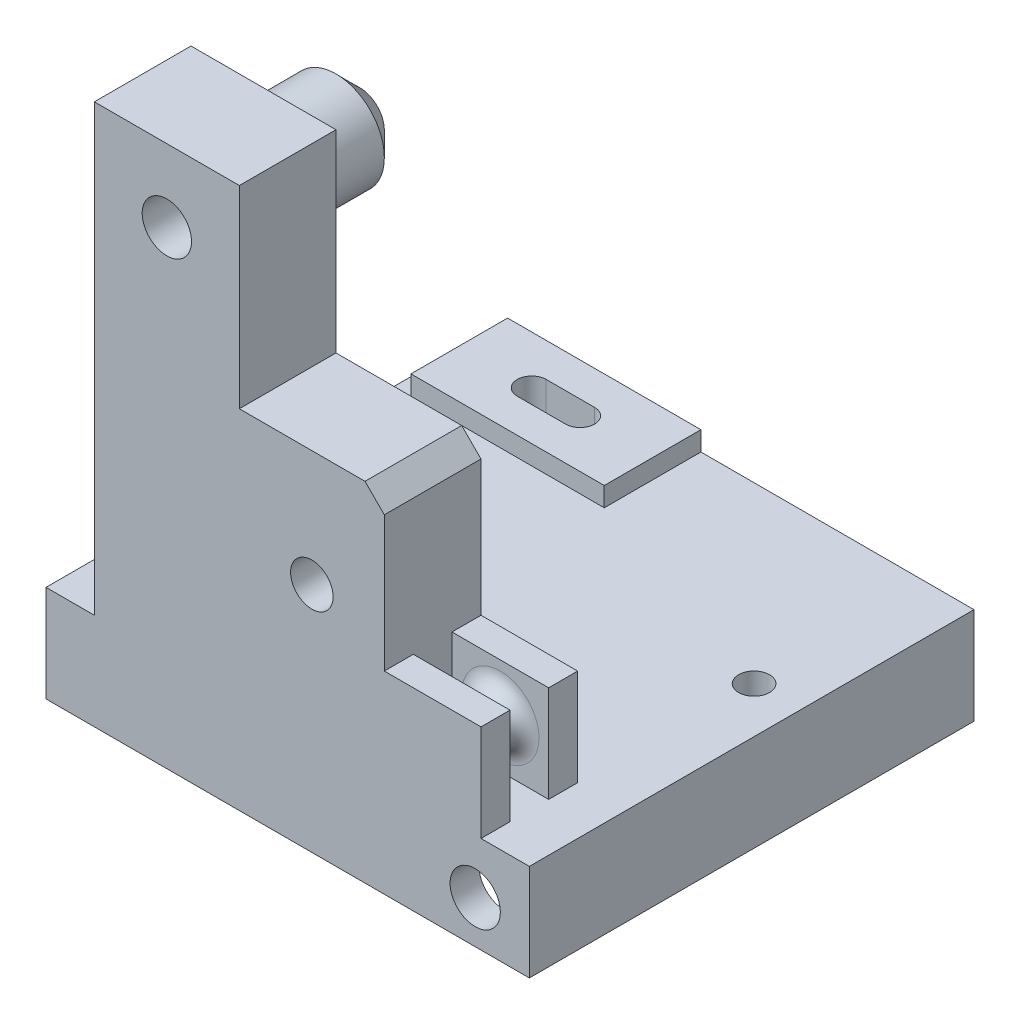
SolidWorks part; units mm, degrees
ref_plane "Front Plane" through (0, 0, 0) normal (0, 0, 1) x (1, 0, 0)
ref_plane "Top Plane" through (0, 0, 0) normal (0, 1, 0) x (1, 0, 0)
ref_plane "Right Plane" through (0, 0, 0) normal (1, 0, 0) x (0, 0, -1)
sketch "Sketch1" plane through (0, 0, 0) normal (0, 0, 1) x (1, 0, 0)
  line L0 (-15, 0) -> (-15, 46)
  line L1 (-15, 46) -> (0, 46)
  line L2 (0, 46) -> (0, 26)
  line L5 (0, 26) -> (15, 26)
  line L6 (15, 26) -> (15, 0)
  line L12 (-15, 0) -> (15, 0)
  circle A0 centre (-7.5, 38.5) radius 2.55
  circle A1 centre (7.5, 14) radius 2.2
  point P8 (0, 0)
  point P12 (-7.5, 46)
  point P16 (7.5, 26)
  dimension "D7" = 5.1
  dimension "D9" = 4.4
  dimension "D1" = 46
  dimension "D2" = 15
  dimension "D3" = 30
  dimension "D6" = 20
  dimension "D8" = 7.5
  dimension "D10" = 12
extrude "Boss-Extrude1" add sketch "Sketch1" along normal blind 6 and the other way blind 4
sketch "Sketch2" plane through (15, 0, 0) normal (1, 0, 0) x (0, 0, -1)
  line L0 (-6, 0) -> (4, 0) construction
  line L1 (-6, 0) -> (-6, 26) construction
  circle A0 centre (-1, 5) radius 2.5
  dimension "D1" = 5
  dimension "D2" = 5
  dimension "D3" = 5
extrude "Boss-Extrude2" [suppressed] add sketch "Sketch2" along normal blind 6
sketch "Sketch3" [suppressed] plane through (21, 0, 0) normal (1, 0, 0) x (0, 0, -1)
  circle A0 centre (-5, 5) radius 4.5
  circle A1 centre (-5, 5) radius 2.5
  circle A2 centre (-5, 5) radius 2.5 construction
  dimension "D1" = 0
  dimension "D2" = 2
extrude "Boss-Extrude3" [suppressed] add sketch "Sketch3" along normal blind 2
ref_plane "Plane1" through (0, 0, -4) normal (0, 0, -1) x (-1, 0, 0)
sketch "Sketch4" plane through (0, 0, -4) normal (0, 0, -1) x (-1, 0, 0)
  line L0 (-15, 0) -> (-15, 10)
  line L1 (-15, 0) -> (-25, 0)
  line L2 (-15, 10) -> (-25, 10)
  line L3 (-25, 0) -> (-25, 10)
  line L4 (-15, 0) -> (-15, 26) construction
  dimension "D1" = 10
  dimension "D2" = 10
extrude "Boss-Extrude4" add sketch "Sketch4" against normal blind 10
sketch "Sketch5" plane through (25, 0, 0) normal (1, 0, 0) x (0, 0, -1)
  line L0 (-3, 10) -> (1, 10)
  line L1 (-3, 10) -> (-3, 0)
  line L2 (1, 10) -> (1, 0)
  line L3 (-3, 0) -> (1, 0)
  line L4 (-6, 10) -> (4, 10) construction
  line L5 (-6, 0) -> (4, 0) construction
  line L7 (-6, 10) -> (4, 10) construction
  point P8 (-1, 10)
  dimension "D1" = 4
extrude "Cut-Extrude1" cut sketch "Sketch5" against normal up to surface (10 mm away) up to face at (15, 18, 1)
sketch "Sketch6" plane through (0, 0, -1) normal (0, 0, 1) x (1, 0, 0)
  line L0 (25, 10) -> (25, 0) construction
  line L1 (15, 10) -> (25, 10) construction
  circle A0 centre (20, 5) radius 2
  dimension "D1" = 4
  dimension "D2" = 5
  dimension "D3" = 5
extrude "Boss-Extrude5" add sketch "Sketch6" along normal up to next
fillet "Fillet1" radius 2 2 edges at (20, 3, 3) (20, 7, -1)
chamfer "Chamfer1" distance 2 angle 45 1 edges at (15, 26, 1)
sketch "Sketch7" plane through (0, 0, 0) normal (0, -1, 0) x (1, 0, 0)
  line L1 (25, 6) -> (-15, 6) construction
  line L2 (25, 6) -> (25, -9.5) construction
  line L3 (25, -9.5) -> (-15, -9.5) construction
  line L4 (-15, 6) -> (-15, -9.5) construction
  line L5 (-15, 6) -> (-15, -4) construction
  line L12 (30, -14.5) -> (-20, -14.5)
  line L24 (-22, -4) -> (22, -4) construction
  line L32 (30, 11) -> (-20, 11) construction
  line L33 (-20, 11) -> (-20, -14.5) construction
  line L34 (30, 11) -> (30, -14.5) construction
  line L35 (-20, -14.5) -> (-20, 6)
  line L36 (-20, 6) -> (30, 6)
  line L37 (30, 6) -> (30, -14.5)
  line L38 (-15, 6) -> (25, 6) construction
  dimension "D2" = 5.5
  dimension "D1" = 5
extrude "Boss-Extrude6" add sketch "Sketch7" along normal blind 10
sketch "Sketch12" plane through (0, 0, 0) normal (0, 1, 0) x (1, 0, 0)
  line L0 (-15, 4) -> (25, 4) construction
  line L3 (-20, 9) -> (-2.5, 9) construction
  line L4 (-20, -6) -> (-20, 14.5) construction
  line L5 (-10.75, 10.5) -> (-5.75, 10.5)
  line L6 (-10.75, 7.5) -> (-5.75, 7.5)
  circle A2 centre (-8.25, 9) radius 1.5 construction
  arc A3 (-10.75, 10.5) -> (-10.75, 7.5) centre (-10.75, 9) ccw
  arc A4 (-5.75, 10.5) -> (-5.75, 7.5) centre (-5.75, 9) cw
  point P12 (-8.25, 7.5)
  point P13 (-8.25, 10.5)
  point P14 (-11.25, 9)
  dimension "D1" = 3
  dimension "D2" = 3
  dimension "D3" = 17.5
  dimension "D4" = 5
  dimension "D5" = 5
sketch "Sketch13" plane through (0, 0, -14.5) normal (0, 0, -1) x (-1, 0, 0)
  line L1 (-30, 0) -> (20, 0)
  line L2 (-30, 0) -> (-30, -10)
  line L3 (-30, -10) -> (20, -10)
  line L4 (20, 0) -> (20, -10)
extrude "Boss-Extrude9" add sketch "Sketch13" along normal blind 25.5
sketch "Sketch14" plane through (0, 0, 0) normal (0, 1, 0) x (1, 0, 0)
  line L0 (-20, 22) -> (30, 22) construction
  line L3 (30, 40) -> (30, -6) construction
  line L4 (-20, -6) -> (-20, 40) construction
  line L7 (0, 4) -> (-15, 4) construction
  dimension "D1" = 18
ref_plane "Plane2" through (0, 0, -22) normal (0, 0, -1) x (-1, 0, 0)
sketch "Sketch16" plane through (0, -10, 0) normal (0, -1, 0) x (1, 0, 0)
  line L8 (27, -37) -> (27, 3)
  line L9 (27, -37) -> (27, 3)
  line L10 (-17, -37) -> (27, -37)
  line L11 (27, 3) -> (-17, 3)
  line L14 (-17, -37) -> (27, -37)
  line L16 (27, 3) -> (-17, 3)
  line L17 (-17, 3) -> (-17, -37)
  line L18 (-17, 3) -> (-17, -37)
  dimension "D1" = 3
extrude "Cut-Extrude3" cut sketch "Sketch16" against normal blind 7
sketch "Sketch17" plane through (0, 0, 6) normal (0, 0, 1) x (1, 0, 0)
  line L1 (-20, 0) -> (30, 0) construction
  line L2 (30, -10) -> (30, 0) construction
  circle A0 centre (24.4, -5.6) radius 2.6
  dimension "D1" = 5.2
  dimension "D2" = 5.6
  dimension "D3" = 5.6
extrude "Cut-Extrude4" cut sketch "Sketch17" against normal up to surface (3 mm away) up to face at (5, -6.5, 3)
sketch "Sketch18" plane through (-20, 0, 0) normal (-1, 0, 0) x (0, 0, 1)
  line L1 (-9, -10) -> (-11, -10)
  line L2 (-9, -10) -> (-9, 0)
  line L3 (-9, 0) -> (-11, 0)
  line L4 (-11, -10) -> (-11, 0)
  line L6 (-40, -10) -> (-40, 0) construction
  line L7 (6, 0) -> (-40, 0) construction
  line L8 (6, -10) -> (-40, -10) construction
  dimension "D1" = 2
  dimension "D2" = 29
extrude "Boss-Extrude11" add sketch "Sketch18" along normal blind 5
fillet "Fillet2" radius 5 1 edges at (-20, -5, -11)
ref_plane "Plane3" through (-7.5, 0, 0) normal (1, 0, 0) x (0, 0, -1)
sketch "Sketch19" plane through (-7.5, 0, 0) normal (-1, 0, 0) x (0, 0, 1)
  line L0 (-4, 38.5) -> (-14, 38.5)
  line L1 (-4, 46) -> (-4, 0) construction
  line L2 (-11.5, 43.5) -> (-4, 43.5)
  line L3 (-4, 43.5) -> (-4, 38.5)
  line L4 (-4, 46) -> (6, 46) construction
  line L5 (-14, 38.5) -> (-14, 41)
  line L6 (-11.5, 43.5) -> (-14, 41)
  dimension "D2" = 135
  dimension "D1" = 7.5
  dimension "D3" = 10
  dimension "D4" = 5
  dimension "D5" = 2.5
revolve "Revolve1" add sketch "Sketch19" angle 360 about L0
sketch "Sketch20" plane through (0, 0, -4) normal (0, 0, 1) x (1, 0, 0)
  circle A1 centre (-7.5, 38.5) radius 2.55
  circle A2 centre (-7.5, 38.5) radius 2.55
  dimension "D1" = 0
extrude "Cut-Extrude5" cut sketch "Sketch20" against normal up to next
fillet "Fillet5" radius 1.5 1 edges at (-12.5, 38.5, -4)
extrude "Cut-Extrude6" cut sketch "Sketch12" against normal blind 3 contours A4 L6 A3 L5
sketch "Sketch22" plane through (0, 0, 0) normal (0, 1, 0) x (1, 0, 0)
  line L0 (22, 4) -> (-22, 4) construction
  line L1 (-18.25, 14) -> (1.75, 14)
  line L2 (-18.25, 14) -> (-18.25, 4)
  line L3 (-18.25, 4) -> (1.75, 4)
  line L4 (1.75, 14) -> (1.75, 4)
  line L5 (-8.25, 4) -> (-8.25, 14) construction
  line L6 (-10.75, 7.5) -> (-5.75, 7.5) construction
  line L7 (-10.75, 10.5) -> (-5.75, 10.5) construction
  line L8 (-10.75, 7.5) -> (-5.75, 7.5)
  line L9 (-10.75, 10.5) -> (-5.75, 10.5)
  line L10 (5.5, 22) -> (-5.5, 22) construction
  line L11 (-10.75, 36.5) -> (-5.75, 36.5)
  line L12 (-10.75, 33.5) -> (-5.75, 33.5)
  line L13 (-18.25, 40) -> (1.75, 40)
  line L14 (1.75, 30) -> (1.75, 40)
  line L15 (-18.25, 30) -> (1.75, 30)
  line L16 (-18.25, 30) -> (-18.25, 40)
  arc A0 (-10.75, 33.5) -> (-10.75, 36.5) centre (-10.75, 35) cw
  arc A2 (-5.75, 7.5) -> (-5.75, 10.5) centre (-5.75, 9) ccw construction
  arc A3 (-10.75, 10.5) -> (-10.75, 7.5) centre (-10.75, 9) ccw construction
  arc A4 (-5.75, 7.5) -> (-5.75, 10.5) centre (-5.75, 9) ccw
  arc A5 (-10.75, 10.5) -> (-10.75, 7.5) centre (-10.75, 9) ccw
  arc A6 (-5.75, 36.5) -> (-5.75, 33.5) centre (-5.75, 35) cw
  point P15 (-8.25, 10.5)
  dimension "D1" = 20
  dimension "D2" = 10
extrude "Boss-Extrude12" add sketch "Sketch22" along normal blind 2
mirror "Mirror2" [suppressed] about plane through (0, 0, -22) normal (0, 0, -1)
sketch "Sketch23" plane through (0, 0, 0) normal (0, 1, 0) x (1, 0, 0)
  line L0 (-20, 22) -> (30, 22) construction
  line L1 (30, 40) -> (30, -6) construction
  circle A0 centre (25.25, 22) radius 1.6
  dimension "D1" = 3.2
  dimension "D2" = 4.75
extrude "Cut-Extrude7" cut sketch "Sketch23" against normal up to next
sketch "Sketch24" plane through (0, 0, 0) normal (0, 1, 0) x (1, 0, 0)
  line L2 (-10.75, 33.5) -> (-5.75, 33.5)
  line L6 (-10.75, 33.5) -> (-5.75, 33.5)
  line L7 (-5.75, 36.5) -> (-10.75, 36.5)
  line L8 (-5.75, 36.5) -> (-10.75, 36.5)
  arc A1 (-10.75, 36.5) -> (-10.75, 33.5) centre (-10.75, 35) ccw
  arc A6 (-10.75, 36.5) -> (-10.75, 33.5) centre (-10.75, 35) ccw
  arc A7 (-5.75, 33.5) -> (-5.75, 36.5) centre (-5.75, 35) ccw
  arc A8 (-5.75, 33.5) -> (-5.75, 36.5) centre (-5.75, 35) ccw
  dimension "D1" = 0
extrude "Cut-Extrude8" cut sketch "Sketch24" against normal through all
